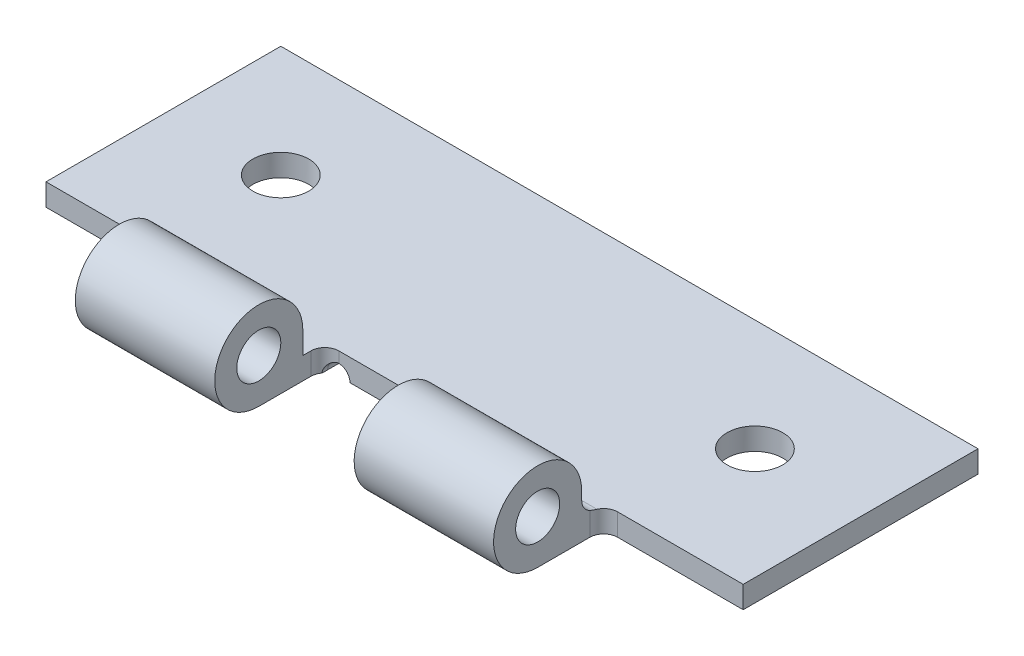
SolidWorks part; units mm, degrees
ref_plane "Front Plane" through (0, 0, 0) normal (0, 0, 1) x (1, 0, 0)
ref_plane "Top Plane" through (0, 0, 0) normal (0, 1, 0) x (1, 0, 0)
ref_plane "Right Plane" through (0, 0, 0) normal (1, 0, 0) x (0, 0, -1)
sketch "Sketch1" plane through (0, 0, 0) normal (0, 1, 0) x (1, 0, 0)
  line L1 (-7.7324, -4.7465) -> (17.2676, -4.7465)
  line L2 (-7.7324, -4.7465) -> (-7.7324, 5.2535)
  line L3 (-7.7324, 5.2535) -> (17.2676, 5.2535)
  line L4 (17.2676, -4.7465) -> (17.2676, 5.2535)
  dimension "D1" = 10
  dimension "D2" = 25
extrude "Base Plate" add sketch "Sketch1" along normal blind 0.79
ref_plane "Inner Plane" through (12.2676, 0, 0) normal (1, 0, 0) x (0, 0, -1)
ref_plane "Middle Plane" through (4.7676, 0, 0) normal (1, 0, 0) x (0, 0, -1)
sketch "Sketch5" plane through (12.2676, 0, 0) normal (1, 0, 0) x (0, 0, -1)
  line L0 (-7.9652, 0.79) -> (-4.7465, 0.79) construction
  line L1 (-3.9565, 1.58) -> (-3.9565, 0.79)
  line L2 (-5.5365, 0) -> (-4.7465, 0)
  arc A1 (-4.7465, 0.79) -> (-5.5365, 0) centre (-5.5365, 0.79) ccw construction
  arc A2 (-3.9565, 1.58) -> (-5.5365, 0) centre (-5.5365, 1.58) ccw
  circle A3 centre (-5.5365, 1.58) radius 0.79
  arc A4 (-4.7465, 0) -> (-3.9565, 0.79) centre (-4.7465, 0.79) ccw
  point P0 (-4.7465, 0)
  point P1 (-4.7465, 0.79)
  point P6 (-7.9652, 0.79)
extrude "Pin Holder" add sketch "Sketch5" against normal blind 5
fillet "Fillet1" radius 0.5 1 edges at (9.7676, 0.79, 3.9565)
sketch "Sketch6" plane through (0, 0.79, 0) normal (0, 1, 0) x (1, 0, 0)
  line L0 (17.2676, -4.7465) -> (17.2676, 5.2535) construction
  line L1 (17.2676, 5.2535) -> (-7.7324, 5.2535) construction
  circle A0 centre (13.2676, 1.2535) radius 1
  dimension "D3" = 2
  dimension "D1" = 4
  dimension "D2" = 4
extrude "Screw Holes" cut sketch "Sketch6" against normal blind 5
mirror "Mirror1" about plane through (4.7676, 0, 0) normal (1, 0, 0) of "Screw Holes", "Pin Holder"
sketch "Sketch7" plane through (0, 0, 4.7465) normal (0, 0, 1) x (1, 0, 0)
  line L0 (12.2676, 0.79) -> (12.2676, 0) construction
  line L1 (17.2676, 0) -> (12.2676, 0)
  line L2 (17.2676, 0) -> (17.2676, 0.79)
  line L3 (17.2676, 0.79) -> (12.2676, 0.79)
  line L4 (12.2676, 0) -> (12.2676, 0.79)
  line L6 (2.2676, 0.79) -> (7.2676, 0.79)
  line L7 (2.2676, 0.79) -> (2.2676, 0)
  line L8 (2.2676, 0) -> (7.2676, 0)
  line L9 (7.2676, 0.79) -> (7.2676, 0)
  line L10 (-7.7324, 0.79) -> (-2.7324, 0.79)
  line L11 (-7.7324, 0.79) -> (-7.7324, 0)
  line L12 (-7.7324, 0) -> (-2.7324, 0)
  line L13 (-2.7324, 0.79) -> (-2.7324, 0)
extrude "Hinge Grooves" cut sketch "Sketch7" against normal blind 1.58
fillet "Fillet2" radius 0.5 4 edges at (-2.7324, 0.395, 3.1665) (12.2676, 0.395, 3.1665) (7.2676, 0.395, 3.1665) (2.2676, 0.395, 3.1665)
sketch "Sketch8" plane through (0, 0, -5.2535) normal (0, 0, -1) x (-1, 0, 0)
  line L0 (-17.2676, 0) -> (7.7324, 0) construction
  line L1 (7.7324, 0.79) -> (7.7324, 0) construction
  circle A0 centre (-2.7676, 0) radius 0.4
  point P0 (-2.7676, 0)
  point P8 (-2.7676, 0)
  dimension "D2" = 0.8
  dimension "D1" = 10.5
sketch "Sketch9" plane through (0, 0, 0) normal (0, -1, 0) x (1, 0, 0)
  line L0 (2.7676, -5.2535) -> (2.7676, 3.1665)
  line L2 (17.2676, -5.2535) -> (-7.7324, -5.2535) construction
  line L3 (-7.7324, 3.1665) -> (-3.2324, 3.1665) construction
  line L4 (-7.7324, -5.2535) -> (-7.7324, 3.1665) construction
  line L5 (2.7676, 3.1665) -> (2.7676, 3.8841)
  dimension "D1" = 10.5
sweep "Wire Groove" cut profiles "Sketch8" path "Sketch9"
